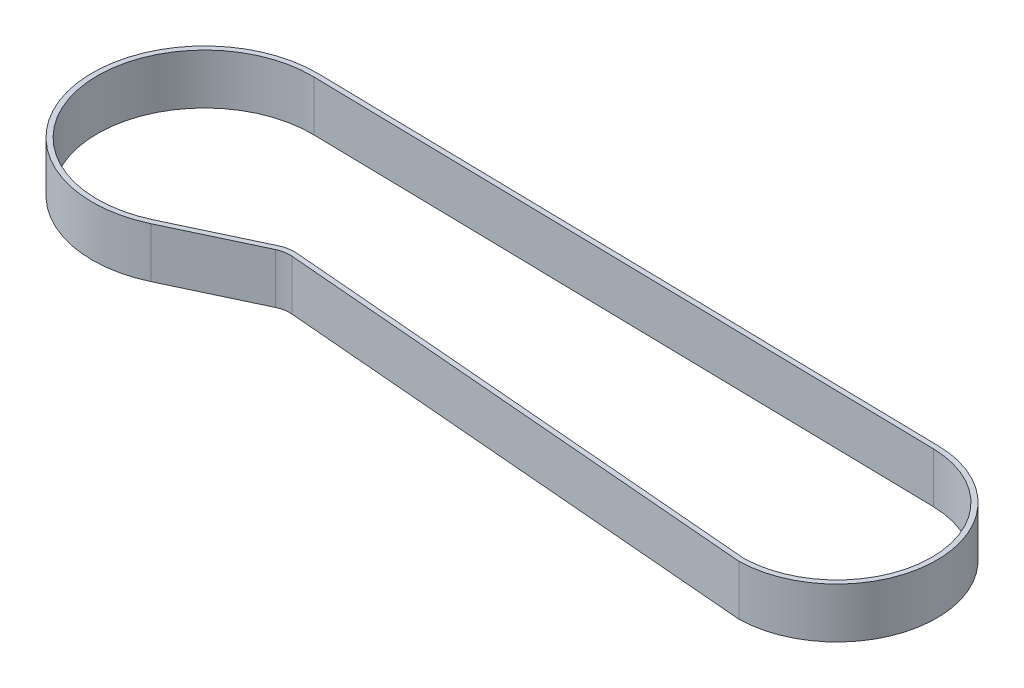
SolidWorks part; units mm, degrees
other "Markup1"
sketch "Sketch2" plane through (-23.4, 0, -23.4) normal (-0.231, -0.9167, -0.326) x (-0.972, 0.232, 0.0366)
sketch "Sketch3" plane through (-22.35, 0, -22.35) normal (-0.231, -0.9167, -0.326) x (-0.972, 0.232, 0.0366)
sketch "Sketch4" plane through (-22.35, 0, -22.35) normal (-0.231, -0.9167, -0.326) x (-0.972, 0.232, 0.0366)
sketch "Sketch5" plane through (-22.35, 0, -22.35) normal (-0.231, -0.9167, -0.326) x (-0.972, 0.232, 0.0366)
material "BUTYL"
ref_plane "Front Plane" through (0, 0, 0) normal (0, 0, 1) x (1, 0, 0)
ref_plane "Top Plane" through (0, 0, 0) normal (0, 1, 0) x (1, 0, 0)
ref_plane "Right Plane" through (0, 0, 0) normal (1, 0, 0) x (0, 0, -1)
sketch "Sketch1" plane through (0, 0, 0) normal (0, 1, 0) x (1, 0, 0)
  line L0 (0, 0) -> (126, 0) construction
  line L1 (0.4151, 21.346) -> (126.3675, 18.8964)
  line L2 (0.4346, 22.3458) -> (126.3869, 19.8962)
  line L5 (9.8233, -18.9559) -> (126.3392, -18.897) construction
  line L6 (10.0644, -19.9557) -> (126.3483, -19.897) construction
  line L7 (126.3392, -18.897) -> (29.4902, -10.8002)
  line L8 (126.3483, -19.897) -> (29.1733, -11.7729)
  line L9 (9.1029, -19.3122) -> (25.9437, -11.3742)
  line L10 (9.5292, -20.2167) -> (26.3701, -12.2787)
  line L11 (0, 0) -> (28.7151, -17.2538) construction
  arc A0 (0.4151, 21.346) -> (9.1029, -19.3122) centre (0, 0) ccw
  arc A1 (126.3392, -18.897) -> (126.3675, 18.8964) centre (126, 0) ccw
  arc A2 (126.3483, -19.897) -> (126.3869, 19.8962) centre (126, 0) ccw
  arc A3 (0.4346, 22.3458) -> (9.5292, -20.2167) centre (0, 0) ccw
  circle A4 centre (0, 0) radius 33.5 construction
  circle A5 centre (28.7151, -17.2538) radius 1.25 construction
  arc A6 (29.1733, -11.7729) -> (26.3701, -12.2787) centre (28.7151, -17.2538) ccw
  arc A8 (29.4902, -10.8002) -> (25.9437, -11.3742) centre (28.7151, -17.2538) ccw
  arc A9 (0.4346, 22.3458) -> (10.0644, -19.9557) centre (0, 0) ccw construction
  arc A10 (0.4151, 21.346) -> (9.8233, -18.9559) centre (0, 0) ccw construction
  dimension "D1" = 42.7
  dimension "D3" = 37.8
  dimension "D5" = 67
  dimension "D6" = 11
  dimension "D7" = 2.5
  dimension "D9" = 1
  dimension "D2" = 126
  dimension "D8" = 31
  dimension "D4" = 1
extrude "Boss-Extrude1" add sketch "Sketch1" along normal blind 10
